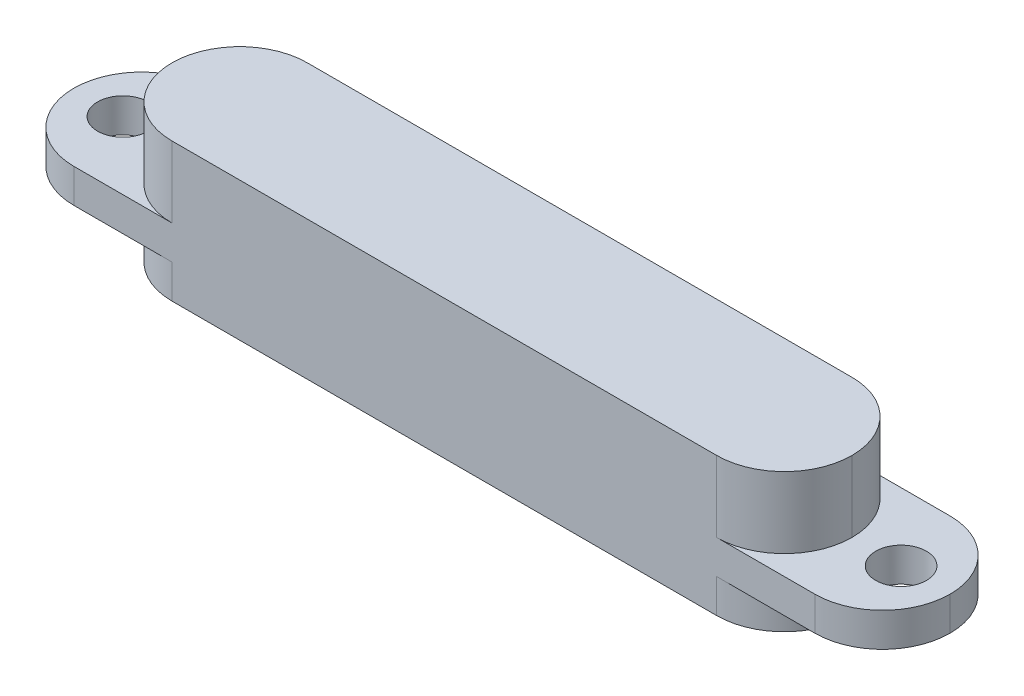
SolidWorks part; units mm, degrees
ref_plane "前视基准面" through (0, 0, 0) normal (0, 0, 1) x (1, 0, 0)
ref_plane "上视基准面" through (0, 0, 0) normal (0, 1, 0) x (1, 0, 0)
ref_plane "右视基准面" through (0, 0, 0) normal (1, 0, 0) x (0, 0, -1)
other "Configuration Table"
sketch "草图1" plane through (0, 0, 0) normal (0, 1, 0) x (1, 0, 0)
  line L1 (-12.95, -2) -> (12.95, -2)
  line L2 (-12.95, -2) -> (-12.95, 2)
  line L3 (-12.95, 2) -> (12.95, 2)
  line L4 (12.95, -2) -> (12.95, 2)
  line L5 (-12.95, -2) -> (12.95, 2) construction
  line L6 (-12.95, 2) -> (12.95, -2) construction
  line L7 (-10.05, -2) -> (10.05, -2)
  line L8 (-10.05, -2) -> (-10.05, 2)
  line L9 (-10.05, 2) -> (10.05, 2)
  line L10 (10.05, -2) -> (10.05, 2)
  line L11 (-10.05, -2) -> (10.05, 2) construction
  line L12 (-10.05, 2) -> (10.05, -2) construction
  point P0 (0, 0)
  point P7 (0, 0)
  dimension "D1" = 4
  dimension "D2" = 25.9
  dimension "D3" = 20.1
extrude "凸台-拉伸1" add sketch "草图1" along normal blind 2.1 contours L8 L9 L10 L7
extrude "凸台-拉伸2" add sketch "草图1<3>" against normal blind 1 contours L2 L3 L4 L1
sketch "草图1<3>" plane through (0, 0, 0) normal (0, 1, 0) x (1, 0, 0) same geometry as "草图1"
extrude "凸台-拉伸4" add sketch "草图1<4>" against normal blind 1 from surface contours L10 L9 L8 L7 starting at face at (0, -1, 0)
sketch "草图1<4>" plane through (0, 0, 0) normal (0, 1, 0) x (1, 0, 0) same geometry as "草图1"
fillet "圆角2" radius 2 4 edges at (12.95, -0.5, 2) (12.95, -0.5, -2) (-12.95, -0.5, 2) (-12.95, -0.5, -2)
fillet "圆角1" radius 2 8 edges at (10.05, 1.05, -2) (10.05, 1.05, 2) (-10.05, 1.05, 2) (-10.05, 1.05, -2) (-10.05, -1.5, -2) (-10.05, -1.5, 2) (10.05, -1.5, 2) (10.05, -1.5, -2)
sketch "草图2" plane through (0, -1, 0) normal (0, -1, 0) x (-1, 0, 0)
  line L0 (12.95, 0) -> (10.05, 0) construction
  line L1 (-10.05, 0) -> (-12.95, 0) construction
  circle A1 centre (11.5, 0) radius 0.75
  arc A2 (8.05, -2) -> (10.05, 0) centre (8.05, 0) ccw construction
  circle A3 centre (-11.5, 0) radius 0.75
  arc A4 (-8.05, 2) -> (-10.05, 0) centre (-8.05, 0) ccw construction
  point P3 (8.0081, 0)
  point P4 (-8.4284, 0)
  point P5 (0, 0)
  point P20 (10.05, 0)
  dimension "D1" = 1.5
extrude "切除-拉伸1" cut sketch "草图2" against normal through all
sketch "草图3" plane through (0, -1, 0) normal (0, -1, 0) x (1, 0, 0)
  line L0 (-5.08, 0) -> (-2.54, 0) construction
  line L5 (-2.54, 0) -> (0, 0) construction
  line L6 (0, 0) -> (2.54, 0) construction
  line L7 (2.54, 0) -> (5.08, 0) construction
  circle A0 centre (0, 0) radius 0.5
  circle A1 centre (2.54, 0) radius 0.5
  circle A2 centre (-2.54, 0) radius 0.5
  circle A3 centre (-5.08, 0) radius 0.5
  circle A4 centre (5.08, 0) radius 0.5
  point P0 (0, 0)
  dimension "D2" = 1
  dimension "D1" = 2.54
extrude "凸台-拉伸3" add sketch "草图3" along normal blind 5.6 from surface starting at face at (0, 2.1, 0)
